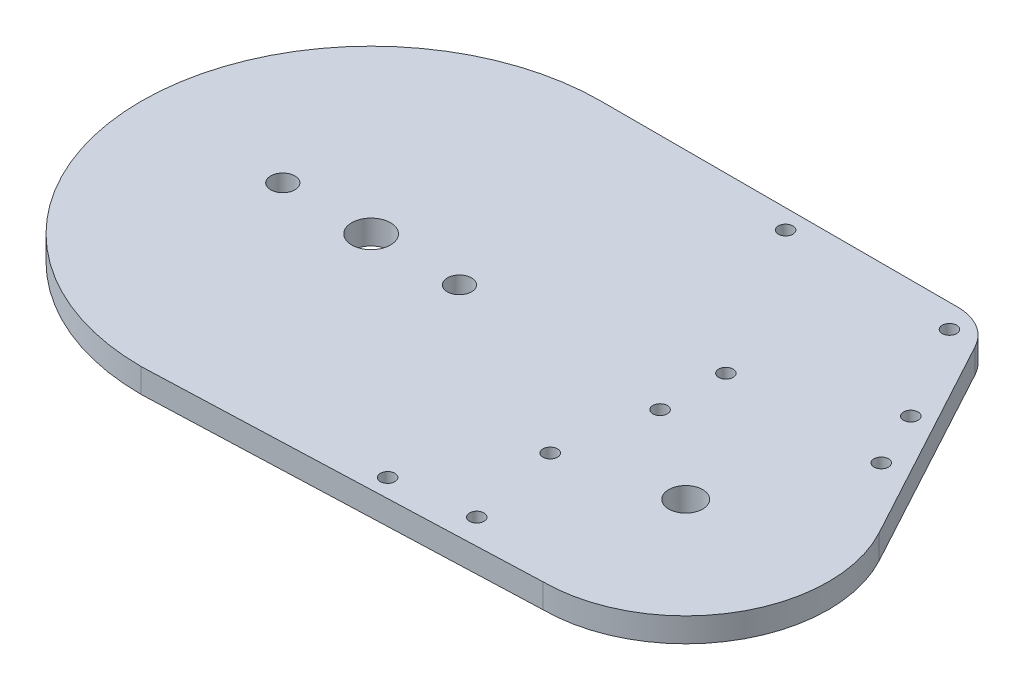
SolidWorks part; units mm, degrees
ref_plane "前视基准面" through (0, 0, 0) normal (0, 0, 1) x (1, 0, 0)
ref_plane "上视基准面" through (0, 0, 0) normal (0, 1, 0) x (1, 0, 0)
ref_plane "右视基准面" through (0, 0, 0) normal (1, 0, 0) x (0, 0, -1)
sketch "Sketch1" plane through (0, 0, 0) normal (0, 1, 0) x (1, 0, 0)
  line L0 (0, 0) -> (0, -15) construction
  line L1 (0, -15) -> (80, -15) construction
  line L2 (0, -47.5) -> (0, -44.5) construction
  line L3 (0, -44.5) -> (94.3585, -44.5) construction
  line L4 (0, -47.5) -> (80, -44.5)
  line L5 (0, 47.5) -> (73.764, 47.5)
  line L6 (82.559, 42.259) -> (105.9453, -0.9611)
  line L7 (0, 0) -> (80, -15) construction
  line L8 (80, -15) -> (61.3033, -1.6048) construction
  line L9 (78.1615, 44.8795) -> (78.8831, 46.0904) construction
  line L10 (78.8831, 46.0904) -> (76.8355, 42.6542) construction
  line L11 (73.764, 47.5) -> (82.559, 42.259) construction
  line L12 (78.1615, 44.8795) -> (73.764, 37.5) construction
  arc A0 (0, 47.5) -> (0, -47.5) centre (0, 0) ccw
  arc A2 (80, -44.5) -> (105.9453, -0.9611) centre (80, -15) ccw
  circle A3 centre (75.0001, 47.5) radius 7.5 construction
  arc A4 (82.559, 42.259) -> (73.764, 47.5) centre (73.764, 37.5) ccw
  circle A5 centre (0, 0) radius 4
  circle A12 centre (80, -15) radius 23 construction
  circle A15 centre (61.3033, -1.6048) radius 1.5
  circle A16 centre (57.7206, -20.7122) radius 1.5
  circle A17 centre (0, 0) radius 18.25 construction
  circle A18 centre (18.25, 0) radius 2.5
  circle A19 centre (-18.25, 0) radius 2.5
  circle A20 centre (80, -15) radius 3.5
  circle A21 centre (76.8355, 42.6542) radius 1.5
  circle A22 centre (88.3547, 23.1429) radius 1.5
  circle A23 centre (42.1373, 43.5) radius 1.5
  circle A24 centre (45.2934, -41.8851) radius 1.5
  circle A25 centre (61.5917, 11.711) radius 1.5
  circle A26 centre (93.688, 11.711) radius 1.5
  circle A27 centre (61.5917, -39.7686) radius 1.5
  point P28 (75, -15)
  dimension "D1" = 95
  dimension "D4" = 25
  dimension "D6" = 15
  dimension "D7" = 10
  dimension "D8" = 8
  dimension "D9" = 46
  dimension "D10" = 3
  dimension "D12" = 4
  dimension "D11" = 36.5
  dimension "D13" = 5
  dimension "D14" = 5
  dimension "D15" = 7
  dimension "D16" = 3
  dimension "D17" = 3
  dimension "D18" = 3
  dimension "D19" = 3
  dimension "D20" = 3
  dimension "D21" = 3
  dimension "D22" = 3
  dimension "D2" = 15
  dimension "D3" = 80
  dimension "D5" = 3
extrude "Boss-Extrude1" add sketch "Sketch1" along normal blind 5
